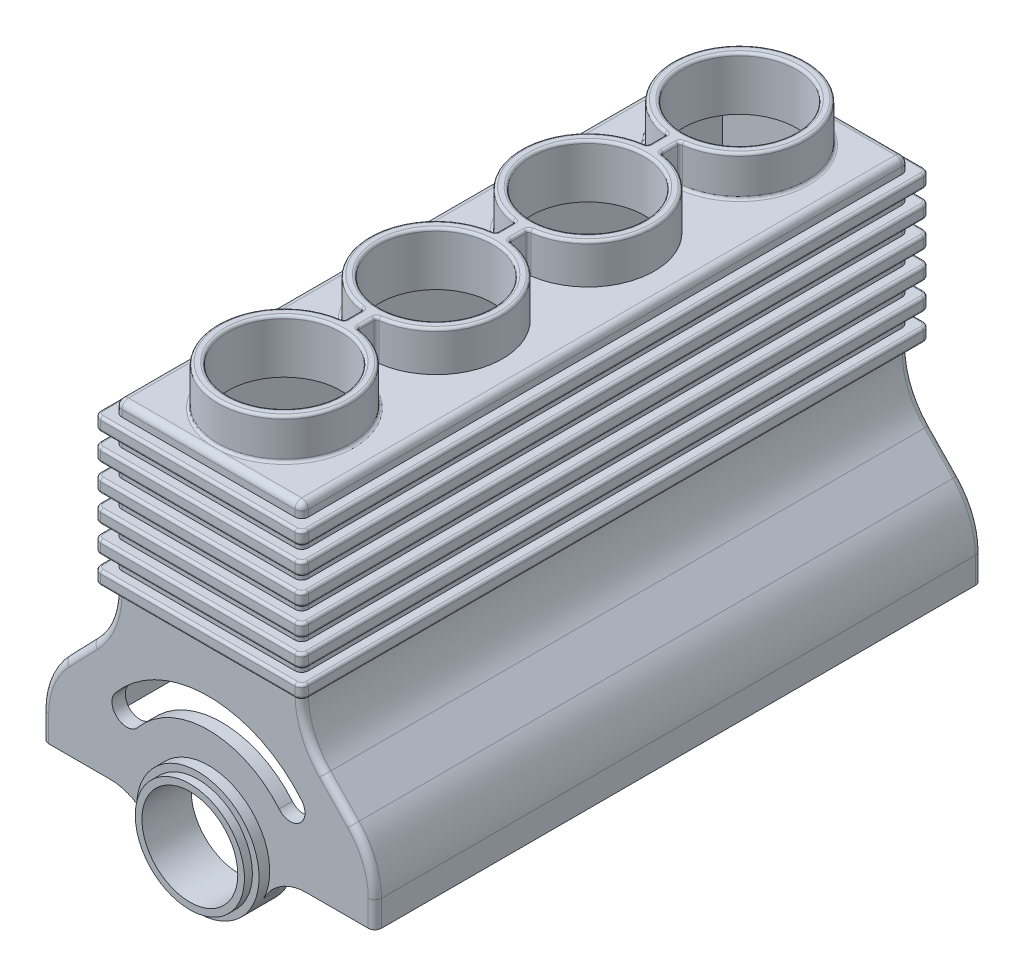
SolidWorks part; units mm, degrees
ref_plane "Front Plane" through (0, 0, 0) normal (0, 0, 1) x (1, 0, 0)
ref_plane "Top Plane" through (0, 0, 0) normal (0, 1, 0) x (1, 0, 0)
ref_plane "Right Plane" through (0, 0, 0) normal (1, 0, 0) x (0, 0, -1)
sketch "Sketch1" plane through (0, 0, 0) normal (0, 0, 1) x (1, 0, 0)
  line L0 (0, 0) -> (0, -82173.5765) construction
  line L1 (0, 0) -> (82173.5765, 0) construction
  line L2 (-36, 0) -> (-125, 0)
  line L3 (-125, 0) -> (-125, 19.5627)
  line L4 (-108.1604, 61.2422) -> (-86.8396, 83.3205)
  line L5 (-70, 125) -> (-70, 250)
  line L6 (0, 0) -> (-82173.5765, 0) construction
  line L7 (70, 125) -> (70, 250)
  line L8 (36, 0) -> (125, 0)
  line L9 (108.1604, 61.2422) -> (86.8396, 83.3205)
  line L10 (125, 0) -> (125, 19.5627)
  line L11 (-70, 250) -> (70, 250)
  arc A0 (36, 0) -> (-36, 0) centre (0, 0) ccw
  arc A1 (-125, 19.5627) -> (-108.1604, 61.2422) centre (-65, 19.5627) cw
  arc A2 (-70, 125) -> (-86.8396, 83.3205) centre (-130, 125) cw
  arc A3 (70, 125) -> (86.8396, 83.3205) centre (130, 125) ccw
  arc A4 (125, 19.5627) -> (108.1604, 61.2422) centre (65, 19.5627) ccw
  point P26 (-123.316, 42.703)
  point P27 (-125, 104.7622)
  point P28 (-123.316, 61.5113)
  point P29 (-76.7137, 120.832)
  point P30 (-80.0046, 125)
  point P31 (123.316, 88.7682)
  point P32 (125, 53.0113)
  point P33 (-90.5501, 83.3205)
  point P34 (-80.6158, 83.3205)
  dimension "D1" = 36
  dimension "D4" = 60
  dimension "D5" = 250
  dimension "D2" = 136
  dimension "D3" = 250
  dimension "D6" = 125
  dimension "D7" = 140
extrude "Boss-Extrude1" add sketch "Sketch1" against normal mid plane 456
fillet "Fillet1" radius 5 24 edges at (0, 250, -228) (-70, 250, 0) (0, 250, 228) (70, 250, 0) (-70, 187.5, -228) (-125, 9.7813, -228) (-120.631, 42.0391, -228) (-97.5, 72.2813, -228) (125, 9.7813, -228) (120.631, 42.0391, -228) (97.5, 72.2813, -228) (74.369, 102.5236, -228) (-125, 9.7813, 228) (-120.631, 42.0391, 228) (-97.5, 72.2813, 228) (-74.369, 102.5236, 228) (125, 9.7813, 228) (120.631, 42.0391, 228) (97.5, 72.2813, 228) (74.369, 102.5236, 228) (-74.369, 102.5236, -228) (70, 187.5, -228) (-70, 187.5, 228) (70, 187.5, 228)
shell "Shell1" thickness 10 removed face at (-94.0118, 0, 0) removed face at (0, 18, 0) removed face at (94.0118, 0, 0)
ref_plane "Plane1" through (0, 240, 0) normal (0, 1, 0) x (1, 0, 0)
sketch "Sketch2" plane through (0, 240, 0) normal (0, 1, 0) x (1, 0, 0)
  line L0 (65, -228) -> (-65, -228) construction
  line L1 (-73, 236) -> (73, 236)
  line L2 (-78, 231) -> (-78, -231)
  line L3 (-73, -236) -> (73, -236)
  line L4 (78, 231) -> (78, -231)
  line L5 (-65, 228) -> (65, 228) construction
  line L6 (70, 223) -> (70, -223) construction
  line L8 (-70, -223) -> (-70, 223) construction
  line L9 (-70, 223) -> (-70, -223) construction
  line L10 (70, 223) -> (70, -223)
  line L11 (65, -228) -> (-65, -228)
  line L12 (-70, 223) -> (-70, -223)
  line L13 (-65, 228) -> (65, 228)
  arc A0 (73, 236) -> (78, 231) centre (73, 231) cw
  arc A1 (-78, -231) -> (-73, -236) centre (-73, -231) ccw
  arc A2 (73, -236) -> (78, -231) centre (73, -231) ccw
  arc A3 (-73, 236) -> (-78, 231) centre (-73, 231) ccw
  arc A4 (70, 223) -> (65, 228) centre (65, 223) ccw construction
  arc A5 (65, -228) -> (70, -223) centre (65, -223) ccw construction
  arc A6 (-70, -223) -> (-65, -228) centre (-65, -223) ccw construction
  arc A7 (-65, 228) -> (-70, 223) centre (-65, 223) ccw construction
  arc A8 (70, 223) -> (65, 228) centre (65, 223) ccw
  arc A9 (65, -228) -> (70, -223) centre (65, -223) ccw
  arc A10 (-70, -223) -> (-65, -228) centre (-65, -223) ccw
  arc A11 (-65, 228) -> (-70, 223) centre (-65, 223) ccw
  dimension "D5" = 5
  dimension "D1" = 8
  dimension "D2" = 8
  dimension "D3" = 8
  dimension "D4" = 8
extrude "Boss-Extrude2" add sketch "Sketch2" against normal blind 10
fillet "Fillet2" radius 2 16 edges at (-76.5355, 230, 234.5355) (-78, 230, 0) (-76.5355, 230, -234.5355) (0, 230, -236) (76.5355, 230, -234.5355) (78, 230, 0) (76.5355, 230, 234.5355) (-76.5355, 240, 234.5355) (-78, 240, 0) (-76.5355, 240, -234.5355) (0, 240, -236) (76.5355, 240, -234.5355) (78, 240, 0) (76.5355, 240, 234.5355) (0, 230, 236) (0, 240, 236)
pattern_linear "LPattern1" count 6 spacing 20 along (0, -1, 0) of "Fillet2", "Boss-Extrude2"
sketch "Sketch3" plane through (0, 250, 0) normal (0, 1, 0) x (1, 0, 0)
  line L1 (0, 0) -> (0, -50000) construction
  line L2 (65, -223) -> (65, 223) construction
  line L4 (-5, -106.7494) -> (-5, -121.2506)
  line L5 (5, -106.7494) -> (5, -121.2506)
  line L6 (-5, 7.2506) -> (-5, -7.2506)
  line L7 (5, 7.2506) -> (5, -7.2506)
  line L10 (-5, 121.2506) -> (-5, 106.7494)
  line L11 (5, 121.2506) -> (5, 106.7494)
  circle A0 centre (0, -171) radius 42.5
  circle A1 centre (0, -57) radius 42.5
  circle A2 centre (0, 57) radius 42.5
  circle A3 centre (0, 171) radius 42.5
  circle A4 centre (0, -171) radius 50
  circle A5 centre (0, -57) radius 50
  circle A6 centre (0, 57) radius 50
  circle A7 centre (0, 171) radius 50
  point P15 (-5, 121.2506)
  point P19 (0, 0)
  dimension "D5" = 85
  dimension "D6" = 100
  dimension "D1" = 57
  dimension "D2" = 114
  dimension "D3" = 114
  dimension "D4" = 114
  dimension "D7" = 10
extrude "Boss-Extrude3" add sketch "Sketch3" along normal blind 30 contours A4 L1 A0 | L1 A4 A0 | A5 L1 A4 L5 | L1 A5 L4 A4 | L1 A5 A1 | A5 L1 A1 | L1 A6 L6 A5 | A6 L1 A5 L7 | A6 L1 A2 | L1 A6 A2 | L1 A7 L10 A6 | A7 L1 A6 L11 | A7 L1 A3 | L1 A7 A3 region at (2.4472, 250, 8.1793) region at (-2.512, 250, 6.8868) region at (-1.118, 250, 10.75) region at (0, 250, -8.4142) region at (-2.5147, 250, 114) region at (2.5147, 250, 114) region at (0, 250, -114) region at (-2.4472, 250, 122.1793) region at (2.4472, 250, 122.1793) region at (-32.5923, 250, -207.0322)
extrude "Cut-Extrude1" cut sketch "Sketch3<4>" against normal blind 60 contours A3 L1 | L1 A3 | A2 L1 | L1 A2 | L1 A1 | A1 L1 | L1 A0 | A0 L1 region at (18.0376, 250, 57) region at (-18.0376, 250, 57) region at (18.0376, 250, 171) region at (-18.0376, 250, 171) region at (0, 250, -57) region at (0, 250, -171)
sketch "Sketch3<4>" plane through (0, 250, 0) normal (0, 1, 0) x (1, 0, 0) same geometry as "Sketch3"
fillet "Fillet3" radius 2 38 edges at (0, 250, 221) (-50, 250, 57) (-50, 250, -57) (0, 250, -221) (-5, 265, -121.2506) (-5, 265, -106.7494) (-5, 250, -114) (-5, 265, -7.2506) (-5, 265, 7.2506) (-5, 250, 0) (-5, 265, 106.7494) (-5, 265, 121.2506) (-5, 250, 114) (5, 265, 121.2506) (5, 265, 106.7494) (5, 250, 114) (5, 265, 7.2506) (5, 265, -7.2506) (5, 250, 0) (5, 265, -106.7494) (5, 265, -121.2506) (5, 250, -114) (-5, 280, 114) (-50, 280, 57) (-5, 280, 0) (-50, 280, -57) (-5, 280, -114) (0, 280, -221) (5, 280, -114) (50, 280, -57) (5, 280, 0) (50, 280, 57) (5, 280, 114) (0, 280, 221) (0, 280, 213.5) (0, 280, 99.5) (0, 280, -14.5) (0, 280, -128.5)
sketch "Sketch4" plane through (0, 0, -228) normal (0, 0, -1) x (-1, 0, 0)
  circle A0 centre (0, 0) radius 46
  circle A1 centre (0, 0) radius 41
  circle A2 centre (0, 0) radius 36
  line M8 (-120, 0) -> (-36, 0)
  arc M9 (-36, 0) -> (36, 0) centre (0, 0) cw
  line M10 (36, 0) -> (120, 0)
  dimension "D1" = 92
  dimension "D2" = 82
  dimension "D3" = 72
extrude "Boss-Extrude4" add sketch "Sketch4" against normal blind 23 and the other way blind 14 contours A2 A1 M8 M10 | A1 M10 M8 M9 region at (-38.5, 0.9168, -228) region at (0, -40.0832, -228)
extrude "Boss-Extrude5" add sketch "Sketch4<3>" against normal blind 18 and the other way blind 8 contours A1 A0 M8 M10 | A1 A0 M10 M8 region at (-43.5, 1.0286, -228) region at (0, -44.9714, -228)
sketch "Sketch4<3>" plane through (0, 0, -228) normal (0, 0, -1) x (-1, 0, 0) same geometry as "Sketch4"
sketch "Sketch5" plane through (0, 0, -228) normal (0, 0, -1) x (-1, 0, 0)
  line L0 (0, 0) -> (0, 80) construction
  line L1 (120, 0) -> (46, 0) construction
  line L2 (73.675, 0) -> (46, 0)
  line L3 (-73.675, 0) -> (-46, 0)
  arc A0 (61.5, 51.164) -> (-61.5, 51.164) centre (0, 0) ccw construction
  arc A1 (69.9563, 58.199) -> (-69.9563, 58.199) centre (0, 0) ccw
  arc A2 (53.0438, 44.1289) -> (-53.0438, 44.1289) centre (0, 0) ccw
  arc A3 (53.0438, 44.1289) -> (69.9563, 58.199) centre (61.5, 51.164) ccw
  arc A4 (-69.9563, 58.199) -> (-53.0438, 44.1289) centre (-61.5, 51.164) ccw
  arc A5 (41.3299, -20.1951) -> (73.675, 0) centre (73.675, -36) cw
  circle A6 centre (0, 0) radius 46 construction
  arc A7 (41.3299, -20.1951) -> (46, 0) centre (0, 0) ccw
  arc A8 (-41.3299, -20.1951) -> (-73.675, 0) centre (-73.675, -36) ccw
  arc A9 (-46, 0) -> (46, 0) centre (0, 0) ccw
  point P4 (0, 80)
  line M3 (46, 0) -> (120, 0)
  line M15 (-120, 0) -> (-46, 0)
  dimension "D1" = 11
  dimension "D2" = 80
  dimension "D4" = 36
  dimension "D3" = 123
extrude "Cut-Extrude2" cut sketch "Sketch5" against normal up to next contours A1 A4 A2 A3 region at (-67.5524, 43.8889, -228)
extrude "Boss-Extrude6" add sketch "Sketch5<3>" against normal blind 10 contours A7 A5 M3 | A9 A8 M15 region at (-51.8612, -4.5291, -228) region at (51.8612, -4.5291, -228)
sketch "Sketch5<3>" plane through (0, 0, -228) normal (0, 0, -1) x (-1, 0, 0) same geometry as "Sketch5"
mirror "Mirror1" about plane through (0, 0, 0) normal (0, 0, 1) of "Boss-Extrude4", "Boss-Extrude5", "Cut-Extrude2", "Boss-Extrude6"
